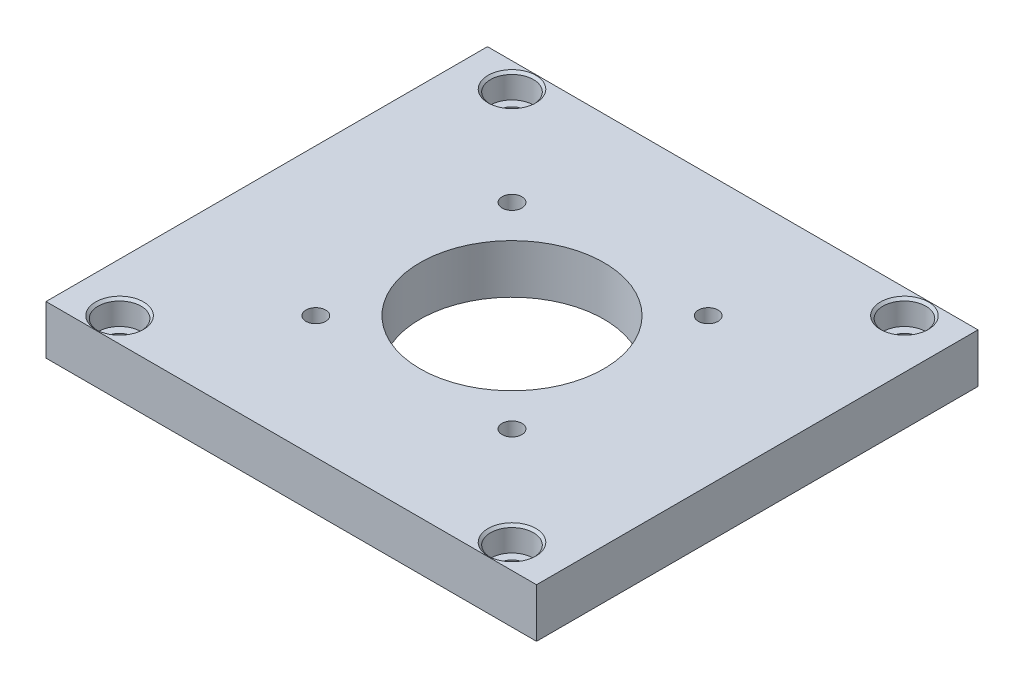
SolidWorks part; units mm, degrees
ref_plane "Front Plane" through (0, 0, 0) normal (0, 0, 1) x (1, 0, 0)
ref_plane "Top Plane" through (0, 0, 0) normal (0, 1, 0) x (1, 0, 0)
ref_plane "Right Plane" through (0, 0, 0) normal (1, 0, 0) x (0, 0, -1)
sketch "Sketch1" plane through (0, 0, 0) normal (0, 1, 0) x (1, 0, 0)
  line L1 (63.5, -57.15) -> (-63.5, -57.15)
  line L2 (63.5, -57.15) -> (63.5, 57.15)
  line L3 (63.5, 57.15) -> (-63.5, 57.15)
  line L4 (-63.5, -57.15) -> (-63.5, 57.15)
  line L5 (63.5, -57.15) -> (-63.5, 57.15) construction
  line L6 (63.5, 57.15) -> (-63.5, -57.15) construction
  point P0 (0, 0)
  dimension "D1" = 127
  dimension "D2" = 114.3
extrude "Boss-Extrude1" add sketch "Sketch1" along normal blind 12.7
sketch "Sketch2" plane through (0, 12.7, 0) normal (0, 1, 0) x (1, 0, 0)
  circle A0 centre (0, 0) radius 23.8125
  dimension "D1" = 47.625
extrude "Cut-Extrude1" cut sketch "Sketch2" against normal through all
sketch "Sketch3" plane through (0, 12.7, 0) normal (0, 1, 0) x (1, 0, 0)
  line L0 (-50.8, -50.8) -> (-50.8, -57.15) construction
  line L1 (-63.5, -57.15) -> (63.5, -57.15) construction
  line L2 (-50.8, 50.8) -> (-50.8, 57.15) construction
  line L3 (63.5, 57.15) -> (-63.5, 57.15) construction
  line L4 (50.8, 50.8) -> (63.5, 50.8) construction
  line L5 (63.5, -57.15) -> (63.5, 57.15) construction
  line L6 (-50.8, 50.8) -> (-63.5, 50.8) construction
  line L7 (-63.5, 57.15) -> (-63.5, -57.15) construction
  point P0 (-50.8, 50.8)
  point P1 (50.8, 50.8)
  point P2 (50.8, -50.8)
  point P3 (-50.8, -50.8)
  dimension "D1" = 101.6
  dimension "D2" = 101.6
  dimension "D3" = 101.6
hole_wizard "CBORE for 1/4 Socket Head Cap Screw1" positions "3DSketch1" profile "Sketch5" counterbore size "1/4" standard "ANSI Inch" end condition through all
sketch3d "3DSketch1"
  point P0 (-50.8, 12.7, -50.8)
  point P3 (50.8, 12.7, -50.8)
  point P6 (50.8, 12.7, 50.8)
  point P9 (-50.8, 12.7, 50.8)
sketch "Sketch5" plane through (-50.8, 12.7, -50.8) normal (1, 0, 0) x (0, 0, 1)
  line L0 (0, 0) -> (0, 12.7)
  line L1 (0, 12.7) -> (3.3782, 12.7)
  line L3 (3.3782, 12.7) -> (3.3782, 6.35)
  line L4 (5.5562, 6.35) -> (3.3782, 6.35)
  line L5 (5.5562, 6.35) -> (5.5562, 0.635)
  line L6 (5.5562, 0.635) -> (6.1912, 0)
  line L7 (6.1912, 0) -> (0, 0)
  line L8 (-5.5562, 0.635) -> (-6.1912, 0) construction
  line L11 (0, -6.35) -> (0, 107.95) construction
  dimension "Thru Hole Dia." = 6.7564
  dimension "Thru Hole Depth" = 12.7
  dimension "C'Bore Dia." = 11.1125
  dimension "C'Bore Depth" = 6.35
  dimension "Near C'Sink Dia." = 12.3825
  dimension "Near C'Sink Angle" = 90
sketch "Sketch6" plane through (0, 12.7, 0) normal (0, 1, 0) x (1, 0, 0)
  line L1 (-25.4, 25.4) -> (25.4, 25.4) construction
  line L2 (-25.4, 25.4) -> (-25.4, -25.4) construction
  line L3 (-25.4, -25.4) -> (25.4, -25.4) construction
  line L4 (25.4, 25.4) -> (25.4, -25.4) construction
  line L5 (-25.4, 25.4) -> (25.4, -25.4) construction
  line L6 (-25.4, -25.4) -> (25.4, 25.4) construction
  point P0 (0, 0)
  dimension "D1" = 50.8
hole_wizard "1/4-20 Tapped Hole1" positions "3DSketch2" profile "Sketch8" tap size "1/4-20" standard "ANSI Inch"
sketch3d "3DSketch2"
  point P0 (-25.4, 12.7, -25.4)
  point P3 (25.4, 12.7, -25.4)
  point P6 (25.4, 12.7, 25.4)
  point P9 (-25.4, 12.7, 25.4)
sketch "Sketch8" plane through (-25.4, 12.7, -25.4) normal (1, 0, 0) x (0, 0, 1)
  line L0 (0, 0) -> (0, 18.0438)
  line L1 (0, 18.0438) -> (2.5527, 16.51)
  line L2 (2.5527, 16.51) -> (2.5527, 0)
  line L5 (2.5527, 0) -> (0, 0)
  line L10 (0, 18.0438) -> (-2.5527, 16.51) construction
  line L11 (0, -6.35) -> (0, 107.95) construction
  dimension "Tap Drill Dia." = 5.1054
  dimension "Tap Drill Depth" = 16.51
  dimension "Drill Angle" = 118
cosmetic thread "Hole Thread5" parameters "D1"=12.7, "D2"=15.875
cosmetic thread "Hole Thread6" parameters "D1"=12.7, "D2"=15.875
cosmetic thread "Hole Thread7" parameters "D1"=12.7, "D2"=15.875
cosmetic thread "Hole Thread8" parameters "D1"=12.7, "D2"=15.875
equation "\"D1@Sketch2\"=\"Pumphole\""
equation "\"D1@Sketch6\" = \"pumpbolts\""
